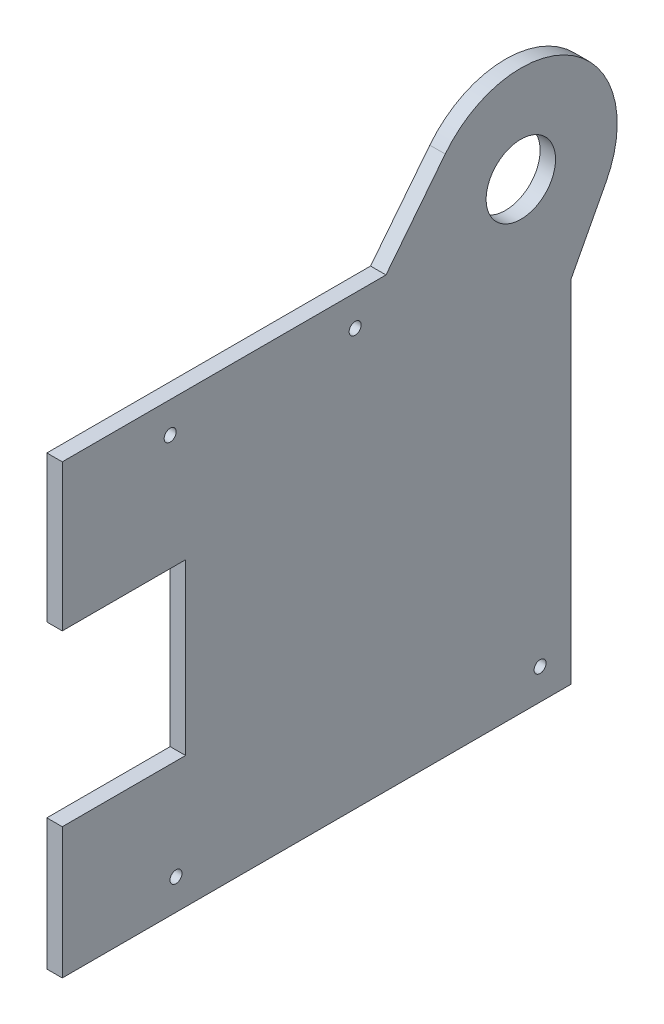
SolidWorks part; units mm, degrees
material "PC High Viscosity"
ref_plane "Front Plane" through (0, 0, 0) normal (0, 0, 1) x (1, 0, 0)
ref_plane "Top Plane" through (0, 0, 0) normal (0, 1, 0) x (1, 0, 0)
ref_plane "Right Plane" through (0, 0, 0) normal (1, 0, 0) x (0, 0, -1)
sketch "Sketch1" plane through (0, 0, 0) normal (1, 0, 0) x (0, 0, -1)
  line L0 (-104.775, -60.325) -> (-104.775, -114.3)
  line L1 (-104.775, 114.3) -> (104.775, 114.3)
  line L2 (-104.775, 114.3) -> (-104.775, 9.525)
  line L3 (-104.775, -114.3) -> (104.775, -114.3)
  line L4 (104.775, 114.3) -> (104.775, -114.3)
  line L5 (-104.775, 114.3) -> (104.775, -114.3) construction
  line L6 (-104.775, -114.3) -> (104.775, 114.3) construction
  line L7 (-104.775, 9.525) -> (-53.975, 9.525)
  line L9 (-104.775, -60.325) -> (-53.975, -60.325)
  line L10 (-53.975, 9.525) -> (-53.975, -60.325)
  line L11 (84.1375, 114.3) -> (84.1375, 90.4875) construction
  line L12 (-53.975, -25.4) -> (-53.975, -114.3) construction
  line L14 (84.1375, 90.4875) -> (84.1375, 61.9125) construction
  line L15 (98.425, 76.2) -> (104.775, 76.2) construction
  circle A0 centre (84.1375, 76.2) radius 14.2875
  point P0 (0, 0)
  dimension "D7" = 28.575
  dimension "D1" = 209.55
  dimension "D2" = 69.85
  dimension "D3" = 228.6
  dimension "D4" = 158.75
  dimension "D5" = 6.35
  dimension "D6" = 190.5
  dimension "D8" = 88.9
extrude "Boss-Extrude1" add sketch "Sketch1" along normal blind 6.35
sketch "Sketch2" plane through (6.35, 0, 0) normal (1, 0, 0) x (0, 0, -1)
  line L1 (-104.775, 114.3) -> (28.575, 114.3)
  line L2 (-104.775, 114.3) -> (-104.775, 69.85)
  line L3 (-104.775, 69.85) -> (28.575, 69.85)
  line L4 (28.575, 114.3) -> (28.575, 69.85)
  dimension "D1" = 44.45
  dimension "D2" = 133.35
extrude "Cut-Extrude1" cut sketch "Sketch2" against normal through all
sketch "Sketch3" plane through (6.35, 0, 0) normal (1, 0, 0) x (0, 0, -1)
  line L0 (28.575, 69.85) -> (52.9799, 100.7825)
  line L1 (104.775, 30.1579) -> (119.2689, 57.7371)
  line L2 (104.775, -114.3) -> (104.775, 114.3) construction
  line L3 (28.575, 69.85) -> (28.575, 114.3)
  line L4 (28.575, 114.3) -> (104.775, 114.3)
  line L5 (104.775, 114.3) -> (104.775, 110.0997)
  line L6 (28.575, 69.85) -> (31.75, 69.85)
  line L7 (31.75, 69.85) -> (51.359, 98.5756)
  circle A0 centre (84.1375, 76.2) radius 14.2875 construction
  circle A1 centre (84.1375, 76.2) radius 14.2875 construction
  circle A2 centre (84.1375, 76.2) radius 39.6875
  line M2 (28.575, 114.3) -> (28.575, 69.85)
  line M10 (104.775, -114.3) -> (104.775, 114.3)
  line M11 (104.775, 114.3) -> (28.575, 114.3)
  dimension "D1" = 25.4
  dimension "D2" = 3.175
extrude "Cut-Extrude2" cut sketch "Sketch3" against normal through all contours A2 L0 M10 M11 M2 | A2 M10 M11 region at (6.35, 99.9615, -41.2172) region at (6.35, 112.9775, -101.807)
extrude "Boss-Extrude2" add sketch "Sketch3<3>" against normal up to surface (6.35 mm away) contours A2 L1 M10 | A2 M10 | L4 A2 region at (6.35, 114.9361, -84.1375) region at (6.35, 76.2, -112.5773) region at (6.35, 41.5222, -108.7517) up to face at (0, 76.2, -98.425)
sketch "Sketch3<3>" plane through (6.35, 0, 0) normal (1, 0, 0) x (0, 0, -1) same geometry as "Sketch3"
fillet "Fillet1" [suppressed] radius 3.175
sketch "Sketch4" plane through (6.35, 0, 0) normal (1, 0, 0) x (0, 0, -1)
  circle A0 centre (-60.325, 57.15) radius 2.4765
  circle A1 centre (15.875, 57.15) radius 2.4765
  circle A2 centre (92.075, -101.6) radius 2.4765
  circle A3 centre (-57.925, -101.6) radius 2.4765
extrude "Cut-Extrude3" cut sketch "Sketch4" against normal through all and the other way blind 2.54
